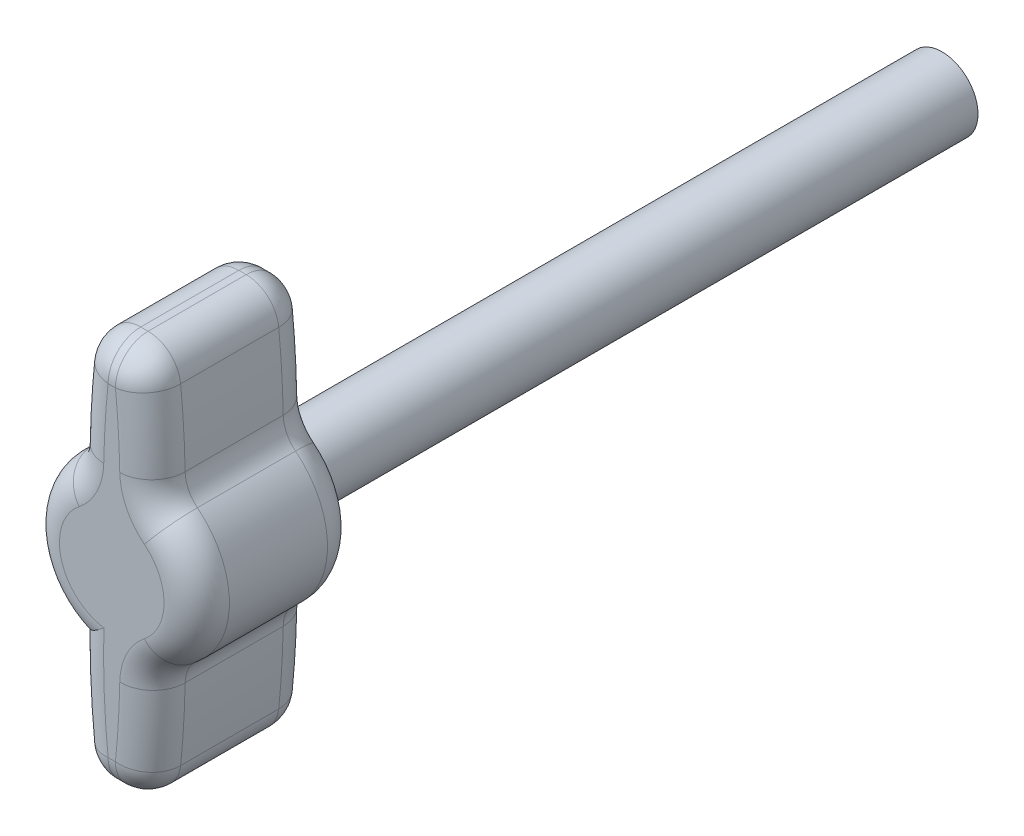
SolidWorks part; units mm, degrees
ref_plane "Front Plane" through (0, 0, 0) normal (0, 0, 1) x (1, 0, 0)
ref_plane "Top Plane" through (0, 0, 0) normal (0, 1, 0) x (1, 0, 0)
ref_plane "Right Plane" through (0, 0, 0) normal (1, 0, 0) x (0, 0, -1)
sketch "Sketch1" plane through (0, 0, 0) normal (0, 0, 1) x (1, 0, 0)
  circle A0 centre (0, 0) radius 2.794
extrude "Extrude1" add sketch "Sketch1" along normal blind 51.816
sketch "Sketch2" plane through (0, 0, 51.816) normal (0, 0, 1) x (1, 0, 0)
  circle A0 centre (0, 0) radius 6.604
extrude "Extrude2" add sketch "Sketch2" along normal blind 12.7
sketch "Sketch3" plane through (0, 0, 64.516) normal (0, 0, 1) x (1, 0, 0)
  line L0 (0, 6.604) -> (-3.175, 6.604) construction
  line L1 (-3.175, 6.604) -> (3.175, 6.604) construction
  line L2 (-3.175, 6.604) -> (-3.175, 5.7907) construction
  line L3 (3.175, 6.604) -> (3.175, 5.7907) construction
  line L4 (-3.175, 15.1226) -> (-2.54, 15.1226) construction
  line L5 (3.175, 15.1226) -> (2.54, 15.1226) construction
  line L6 (-2.54, 15.1226) -> (2.54, 15.1226)
  line L7 (2.54, -15.1226) -> (-2.54, -15.1226)
  circle A0 centre (0, 0) radius 6.604 construction
  arc A1 (-3.175, 5.7907) -> (3.175, 5.7907) centre (0, 0) cw
  arc A2 (-3.175, 5.7907) -> (-2.54, 15.1226) centre (65.7126, 5.7907) cw
  arc A3 (3.175, 5.7907) -> (2.54, 15.1226) centre (-65.7126, 5.7907) ccw
  arc A4 (3.175, -5.7907) -> (2.54, -15.1226) centre (-65.7126, -5.7907) cw
  arc A5 (-3.175, -5.7907) -> (-2.54, -15.1226) centre (65.7126, -5.7907) ccw
  arc A6 (3.175, -5.7907) -> (-3.175, -5.7907) centre (0, 0) cw
extrude "Extrude3" add sketch "Sketch3" against normal up to surface (12.7 mm away) up to face at (6.604, 0, 51.816)
fillet "Fillet1" radius 2.54 4 edges at (-2.54, -15.1226, 58.166) (2.54, -15.1226, 58.166) (-2.54, 15.1226, 58.166) (2.54, 15.1226, 58.166)
fillet "Fillet2" radius 2.54 27 edges at (6.604, 0, 51.816) (-3.0845, -9.3213, 51.816) (-1.9881, -14.4683, 51.816) (0, -15.1226, 51.816) (1.9881, -14.4683, 51.816) (-3.0845, 9.3213, 51.816) (-1.9881, 14.4683, 51.816) (0, 15.1226, 51.816) (1.9881, 14.4683, 51.816) (3.175, -5.7907, 58.166) (3.0845, -9.3213, 51.816) (3.175, 5.7907, 58.166) (3.0845, 9.3213, 51.816) (-6.604, 0, 64.516) (-3.0845, 9.3213, 64.516) (-1.9881, 14.4683, 64.516) (0, 15.1226, 64.516) (1.9881, 14.4683, 64.516) (3.0845, 9.3213, 64.516) (6.604, 0, 64.516) (3.0845, -9.3213, 64.516) (1.9881, -14.4683, 64.516) (0, -15.1226, 64.516) (-1.9881, -14.4683, 64.516) (-3.0845, -9.3213, 64.516) (-6.604, 0, 51.816) (-3.175, 5.7907, 58.166)
